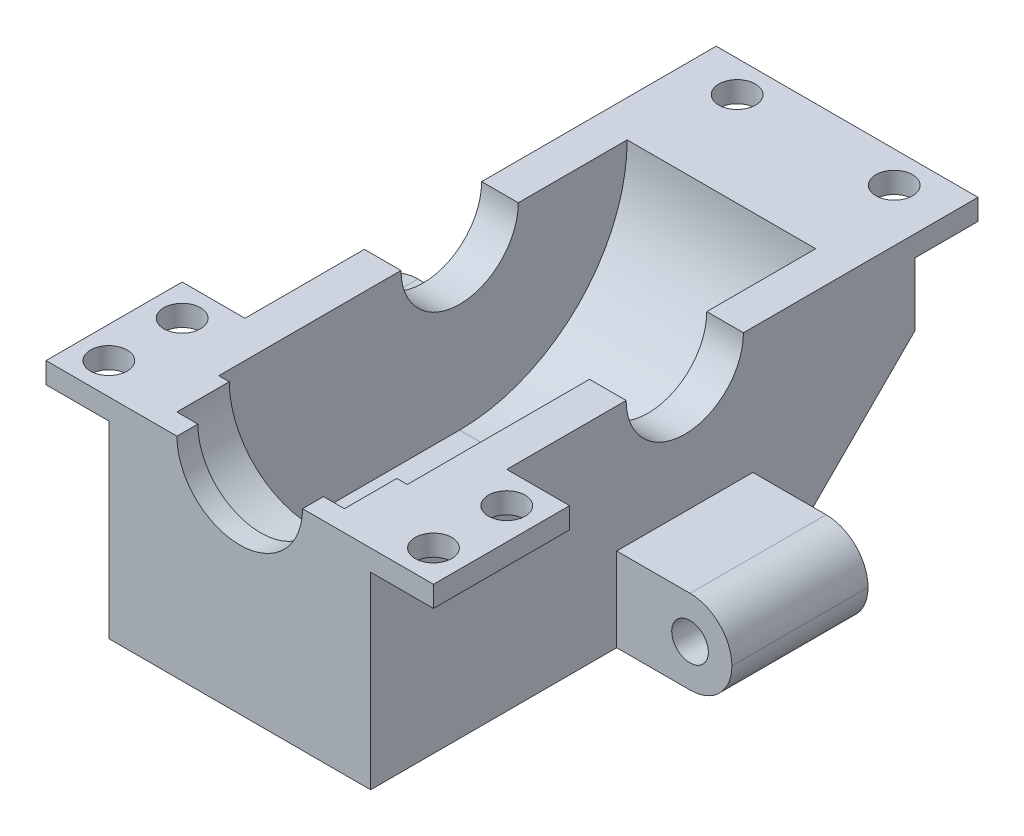
SolidWorks part; units mm, degrees
ref_plane "Alzado" through (0, 0, 0) normal (0, 0, 1) x (1, 0, 0)
ref_plane "Planta" through (0, 0, 0) normal (0, 1, 0) x (1, 0, 0)
ref_plane "Vista lateral" through (0, 0, 0) normal (1, 0, 0) x (0, 0, -1)
sketch "Croquis2" plane through (0, 0, 0) normal (0, 1, 0) x (1, 0, 0)
  line L1 (-12.5, -25) -> (12.5, -25)
  line L2 (-12.5, -25) -> (-12.5, 25)
  line L3 (-12.5, 25) -> (12.5, 25)
  line L4 (12.5, -25) -> (12.5, 25)
  line L5 (-12.5, -25) -> (12.5, 25) construction
  line L6 (-12.5, 25) -> (12.5, -25) construction
  point P0 (0, 0)
  dimension "D1" = 25
  dimension "D2" = 50
extrude "Saliente-Extruir2" add sketch "Croquis2" along normal blind 20
sketch "Croquis19" plane through (0, 0, 25) normal (0, 0, 1) x (1, 0, 0)
  line L1 (-12.5, 20) -> (12.5, 20)
  line L2 (-12.5, 20) -> (-12.5, 0)
  line L3 (-12.5, 0) -> (12.5, 0)
  line L4 (12.5, 20) -> (12.5, 0)
extrude "Saliente-Extruir8" add sketch "Croquis19" along normal blind 6
sketch "Croquis4" plane through (0, 0, 0) normal (1, 0, 0) x (0, 0, -1)
  line L0 (-31, 20) -> (25, 20) construction
  line L2 (-3, 4) -> (-26, 4)
  line L3 (-26, 4) -> (-26, 20)
  line L4 (-31, 20) -> (25, 20) construction
  line L5 (-26, 20) -> (13, 20)
  line L6 (25, 20) -> (25, 0) construction
  arc A0 (-3, 4) -> (13, 20) centre (-3, 20) ccw
  dimension "D1" = 12
  dimension "D2" = 23
extrude "Cortar-Extruir1" cut sketch "Croquis4" against normal mid plane 18 contours A0 | A0 region at (0, 12.4273, 8.0375)
sketch "Croquis5" plane through (0, 0, 0) normal (1, 0, 0) x (0, 0, -1)
  line L0 (-31, 20) -> (25, 20) construction
  line L1 (-8.6, 20) -> (2.6, 20)
  circle A0 centre (-3, 20) radius 5.6
  dimension "D1" = 11.2
extrude "Cortar-Extruir2" cut sketch "Croquis5" against normal through all both and the other way through all contours L1 A0 region at (0, 17.6233, 3)
sketch "Croquis9" plane through (0, 0, 31) normal (0, 0, 1) x (1, 0, 0)
  line L0 (12.5, 20) -> (-12.5, 20) construction
  circle A0 centre (0, 20) radius 8
  point P2 (0, 0)
  dimension "D1" = 16
extrude "Cortar-Extruir3" cut sketch "Croquis9" against normal blind 5
sketch "Croquis22" plane through (0, 0, 31) normal (0, 0, 1) x (1, 0, 0)
  line L0 (6, 20) -> (12.5, 20)
  line L1 (-12.5, 0) -> (12.5, 0)
  line L2 (-12.5, 0) -> (-12.5, 20)
  line L3 (-12.5, 20) -> (-6, 20)
  line L4 (12.5, 0) -> (12.5, 20)
  line L5 (-9, 20) -> (9, 20) construction
  arc A0 (-6, 20) -> (6, 20) centre (0, 20) ccw
  point P7 (0, 17)
  point P10 (0, 0)
  dimension "D1" = 12
extrude "Saliente-Extruir9" add sketch "Croquis22" along normal blind 2
sketch "Croquis11" plane through (12.5, 0, 0) normal (1, 0, 0) x (0, 0, -1)
  line L1 (-33, 18) -> (-20, 18)
  line L2 (-33, 18) -> (-33, 20)
  line L3 (-33, 20) -> (-20, 20)
  line L4 (-20, 18) -> (-20, 20)
  line L5 (-33, 20) -> (-8.6, 20) construction
  point P4 (-33, 20)
  dimension "D1" = 2
  dimension "D2" = 13
extrude "Saliente-Extruir4" add sketch "Croquis11" along normal blind 6
sketch "Croquis13" plane through (-12.5, 0, 0) normal (-1, 0, 0) x (0, 0, 1)
  line L1 (33, 20) -> (20, 20)
  line L2 (33, 20) -> (33, 18)
  line L3 (33, 18) -> (20, 18)
  line L4 (20, 20) -> (20, 18)
  line L5 (8.6, 20) -> (33, 20) construction
  point P4 (33, 20)
  dimension "D1" = 2
  dimension "D3" = 13
extrude "Saliente-Extruir5" add sketch "Croquis13" along normal blind 6
sketch "Croquis16" plane through (0, 20, 0) normal (0, 1, 0) x (1, 0, 0)
  line L1 (12.5, 2.6) -> (12.5, 25) construction
  line L2 (-12.5, 25) -> (-12.5, 2.6) construction
  line L3 (12.5, 25) -> (-12.5, 25) construction
  circle A0 centre (-7.5, 22) radius 1.75
  circle A1 centre (7.5, 22) radius 1.75
  dimension "D5" = 3.5
  dimension "D6" = 3.5
  dimension "D1" = 3
  dimension "D2" = 3
  dimension "D3" = 5
  dimension "D4" = 5
extrude "Cortar-Extruir6" cut sketch "Croquis16" against normal through all
sketch "Croquis17" plane through (-12.5, 0, 0) normal (-1, 0, 0) x (0, 0, 1)
  line L0 (3, 0) -> (3, 20) construction
  line L2 (-3.5, 0) -> (9.5, 0)
  line L3 (-3.5, 0) -> (-3.5, 8)
  line L4 (-3.5, 8) -> (9.5, 8)
  line L5 (9.5, 0) -> (9.5, 8)
  line L6 (-25, 0) -> (33, 0) construction
  point P2 (3, 0)
  dimension "D1" = 8
  dimension "D4" = 13
extrude "Saliente-Extruir7" add sketch "Croquis17" along normal blind 11
fillet "Redondeo1" radius 4 2 edges at (-23.5, 0, 3) (-23.5, 8, 3)
sketch "Croquis12" plane through (0, 20, 0) normal (0, 1, 0) x (1, 0, 0)
  line L0 (18.5, -20) -> (18.5, -33) construction
  line L1 (18.5, -20) -> (12.5, -20) construction
  line L3 (18.5, -33) -> (6, -33) construction
  circle A0 centre (15.5, -23) radius 1.75
  circle A1 centre (15.5, -30) radius 1.75
  dimension "D1" = 3.5
  dimension "D4" = 3.5
  dimension "D5" = 3
  dimension "D3" = 3
  dimension "D2" = 3
extrude "Cortar-Extruir4" cut sketch "Croquis12" against normal through all
sketch "Croquis14" plane through (0, 20, 0) normal (0, 1, 0) x (1, 0, 0)
  line L0 (-18.5, -20) -> (-18.5, -33) construction
  line L1 (-18.5, -33) -> (-18.5, -20) construction
  line L2 (-18.5, -20) -> (-12.5, -20) construction
  line L3 (-18.5, -33) -> (-12.5, -33) construction
  circle A0 centre (-15.5, -23) radius 1.75
  circle A1 centre (-15.5, -30) radius 1.75
  dimension "D1" = 3.5
  dimension "D4" = 3.5
  dimension "D2" = 3
  dimension "D3" = 3
  dimension "D5" = 3
  dimension "D6" = 3
extrude "Cortar-Extruir5" cut sketch "Croquis14" against normal through all
sketch "Croquis18" plane through (0, 0, -3.5) normal (0, 0, -1) x (-1, 0, 0)
  circle A0 centre (19.5, 4) radius 1.75
  dimension "D1" = 3.5
extrude "Cortar-Extruir7" cut sketch "Croquis18" against normal through all
mirror "Simetría1" about plane through (0, 0, 0) normal (1, 0, 0) of "Cortar-Extruir7", "Saliente-Extruir7", "Redondeo1"
sketch "Croquis23" plane through (0, 0, -25) normal (0, 0, -1) x (-1, 0, 0)
  line L0 (12.5, 20) -> (12.5, 0) construction
  line L1 (-12.5, 0) -> (12.5, 0)
  line L2 (-12.5, 0) -> (-12.5, 18)
  line L3 (-12.5, 18) -> (12.5, 18)
  line L4 (12.5, 0) -> (12.5, 18)
  line L5 (-12.5, 20) -> (12.5, 20) construction
  dimension "D1" = 2
extrude "Cortar-Extruir9" cut sketch "Croquis23" against normal blind 6
chamfer "Chaflán1" distance 12 angle 45 1 edges at (0, 0, -19)
